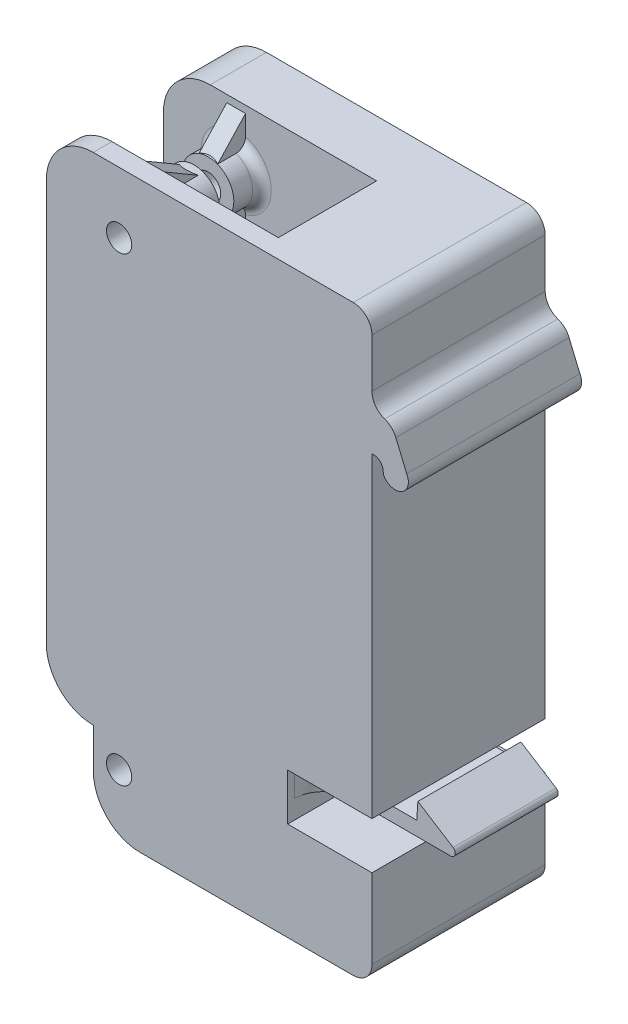
SolidWorks part; units mm, degrees
ref_plane "Alzado" through (0, 0, 0) normal (0, 0, 1) x (1, 0, 0)
ref_plane "Planta" through (0, 0, 0) normal (0, 1, 0) x (1, 0, 0)
ref_plane "Vista lateral" through (0, 0, 0) normal (1, 0, 0) x (0, 0, -1)
sketch "Croquis1" plane through (0, 0, 0) normal (0, 0, 1) x (1, 0, 0)
  line L0 (0, 23.25) -> (0, -23.25)
  circle A0 centre (0, 24.6) radius 1.35
  circle A1 centre (0, -24.6) radius 1.35
  circle A2 centre (0, 24.6) radius 2.75
  circle A3 centre (0, -24.6) radius 2.75
  point P7 (0, 23.25)
  point P8 (0, -23.25)
  dimension "D2" = 2.7
  dimension "D3" = 5.5
  dimension "D4" = 5.5
  dimension "D1" = 46.5
extrude "Saliente-Extruir1" add sketch "Croquis1" against normal blind 6 contours A2 A0 | A3 A1 region at (-1.8895, 26.4895, 0) region at (1.8895, -22.7105, 0)
ref_plane "Plano1" through (0, 0, 1.5) normal (0, 0, 1) x (1, 0, 0)
sketch "Croquis2" plane through (0, 0, 1.5) normal (0, 0, 1) x (1, 0, 0)
  circle A0 centre (0, -24.6) radius 2.75 construction
  circle A1 centre (0, 24.6) radius 2.75 construction
  circle A2 centre (0, -24.6) radius 2.75
  circle A3 centre (0, 24.6) radius 2.75
  circle A4 centre (0, 24.6) radius 1.35 construction
  circle A5 centre (0, -24.6) radius 1.35 construction
  circle A6 centre (0, 24.6) radius 1.35
  circle A7 centre (0, -24.6) radius 1.35
extrude "Saliente-Extruir2" add sketch "Croquis2" along normal blind 8 separate body
ref_plane "Plano2" through (0, 0, 9.5) normal (0, 0, 1) x (1, 0, 0)
sketch "Croquis4" plane through (0, 0, 9.5) normal (0, 0, 1) x (1, 0, 0)
  line L0 (0, 24.6) -> (0, -24.6) construction
  line L1 (15, -31.1189) -> (-7.768, -31.1189)
  line L2 (15, -31.1189) -> (15, 31.1189)
  line L3 (15, 31.1189) -> (-7.768, 31.1189)
  line L4 (-7.768, -31.1189) -> (-7.768, 31.1189)
  line L5 (15, -31.1189) -> (-7.768, 31.1189) construction
  line L6 (15, 31.1189) -> (-7.768, -31.1189) construction
  circle A0 centre (0, -24.6) radius 2.75 construction
  circle A1 centre (0, 24.6) radius 2.75 construction
  circle A2 centre (0, -24.6) radius 2.75
  circle A3 centre (0, 24.6) radius 2.75
  point P0 (3.616, 0)
  dimension "D1" = 15
extrude "Saliente-Extruir3" add sketch "Croquis4" against normal blind 2
sketch "Croquis5" plane through (0, 0, 7.5) normal (0, 0, -1) x (-1, 0, 0)
  line L1 (2.75, -21.85) -> (7.768, -21.85)
  line L2 (2.75, -21.85) -> (2.75, -31.1189)
  line L3 (2.75, -31.1189) -> (7.768, -31.1189)
  line L4 (7.768, -21.85) -> (7.768, -31.1189)
  circle A0 centre (0, -24.6) radius 2.75 construction
  circle A1 centre (0, -24.6) radius 2.75 construction
  point P5 (0, -21.85)
extrude "Cortar-Extruir1" cut sketch "Croquis5" against normal blind 2
fillet "Redondeo1" radius 5 3 edges at (-7.768, 31.1189, 8.5) (-2.75, -31.1189, 8.5) (-7.768, -21.85, 8.5)
ref_plane "Plano3" through (0, 0, -6) normal (0, 0, -1) x (-1, 0, 0)
sketch "Croquis6" plane through (0, 0, -6) normal (0, 0, -1) x (-1, 0, 0)
  line L0 (0, 0) -> (7.768, 0) construction
  line L1 (2.768, -31.1189) -> (-15, -31.1189)
  line L2 (-15, 31.1189) -> (-15, -31.1189)
  line L8 (7.768, -26.1189) -> (7.768, 26.1189)
  line L9 (2.768, 31.1189) -> (-15, 31.1189)
  arc A0 (7.768, -26.1189) -> (2.768, -31.1189) centre (2.768, -26.1189) cw
  circle A1 centre (0, -24.6) radius 2.75 construction
  circle A2 centre (0, 24.6) radius 2.75 construction
  circle A3 centre (0, -24.6) radius 2.75
  arc A11 (7.768, 26.1189) -> (2.768, 31.1189) centre (2.768, 26.1189) ccw
  circle A12 centre (0, 24.6) radius 2.75
extrude "Saliente-Extruir4" add sketch "Croquis6" against normal blind 3
sketch "Croquis7" plane through (0, 0, -6) normal (0, 0, -1) x (-1, 0, 0)
  line L4 (7.768, -26.1189) -> (7.768, 26.1189)
  line L5 (2.768, 31.1189) -> (-15, 31.1189)
  line L6 (-15, 31.1189) -> (-15, -31.1189)
  line L7 (-15, -31.1189) -> (2.768, -31.1189)
  line L8 (7.768, -26.1189) -> (7.768, 26.1189)
  line L9 (2.768, 31.1189) -> (-15, 31.1189)
  line L10 (-15, 31.1189) -> (-15, -31.1189)
  line L11 (-15, -31.1189) -> (2.768, -31.1189)
  circle A0 centre (0, -24.6) radius 1.35 construction
  circle A1 centre (0, 24.6) radius 1.35 construction
  arc A2 (2.768, -31.1189) -> (7.768, -26.1189) centre (2.768, -26.1189) ccw
  arc A3 (7.768, 26.1189) -> (2.768, 31.1189) centre (2.768, 26.1189) ccw
  arc A4 (2.768, -31.1189) -> (7.768, -26.1189) centre (2.768, -26.1189) ccw
  arc A5 (7.768, 26.1189) -> (2.768, 31.1189) centre (2.768, 26.1189) ccw
  circle A6 centre (0, -24.6) radius 1.35
  circle A7 centre (0, 24.6) radius 1.35
  dimension "D1" = 0
extrude "Saliente-Extruir6" add sketch "Croquis7" along normal blind 3
ref_plane "Plano4" through (15, 0, 0) normal (1, 0, 0) x (0, 0, -1)
sketch "Croquis9" plane through (15, 0, 0) normal (1, 0, 0) x (0, 0, -1)
  line L1 (-9.5, 31.1189) -> (9, 31.1189)
  line L2 (-9.5, 31.1189) -> (-9.5, -31.1189)
  line L3 (-9.5, -31.1189) -> (9, -31.1189)
  line L4 (9, 31.1189) -> (9, -31.1189)
extrude "Saliente-Extruir7" add sketch "Croquis9" along normal blind 12
ref_plane "Plano5" through (0, 0, 0.25) normal (0, 0, 1) x (1, 0, 0)
sketch "Croquis10" plane through (0, 0, -9) normal (0, 0, -1) x (-1, 0, 0)
  line L0 (-27, 21.2078) -> (-27.7857, 21.2078)
  line L1 (-27, -31.1189) -> (-27, 31.1189) construction
  line L2 (-27.7857, 21.2078) -> (-28.018, 18.5571)
  line L3 (-29.036, 18.5897) -> (-29.036, 23.6091)
  line L4 (-28.2044, 25.2323) -> (-27, 26.0992)
  line L5 (-27, 26.0992) -> (-27, 21.2078)
  arc A0 (-28.018, 18.5571) -> (-29.036, 18.5897) centre (-28.5261, 18.6017) cw
  arc A1 (-29.036, 23.6091) -> (-28.2044, 25.2323) centre (-27.036, 23.6091) cw
  dimension "D1" = 2
sketch "Croquis11" plane through (0, 0, 0.25) normal (0, 0, 1) x (1, 0, 0)
  line L5 (27, 22.4051) -> (27, 18.1284)
  line L6 (30.7136, 18.1284) -> (29.1816, 21.7903)
  line L7 (28.0402, 18.1284) -> (28.2529, 16.762)
  line L8 (27, 18.1284) -> (28.0402, 18.1284)
  line L9 (29.1816, 21.7903) -> (27, 22.4051)
  line L10 (27, 31.1189) -> (27, -31.1189) construction
  arc A3 (28.2529, 16.762) -> (30.7136, 18.1284) centre (29.4832, 17.4452) ccw
extrude "Saliente-Extruir8" add sketch "Croquis11" along normal mid plane 18.5
sketch "Croquis12" plane through (0, 0, 0.25) normal (0, 0, 1) x (1, 0, 0)
  line L0 (21, -17.1189) -> (28.0356, -17.1189)
  line L1 (2.25, -31.1189) -> (27, -31.1189) construction
  line L2 (28.0356, -17.1189) -> (28.1533, -15.3189)
  line L3 (28.1533, -15.3189) -> (28.2001, -15.3485)
  line L4 (27.7384, -17.1189) -> (28.8359, -17.1189) construction
  line L5 (27, -17.1189) -> (27, -18.6189)
  line L6 (27, 18.1284) -> (27, -31.1189) construction
  line L7 (27, -18.6189) -> (33.3679, -18.6189)
  line L8 (33.3679, -18.6189) -> (28.2001, -15.3485)
  line L9 (27, -18.6189) -> (21, -18.6189)
  line L10 (21, -18.6189) -> (21, -17.1189)
  dimension "D1" = 14
  dimension "D2" = 1.8
  dimension "D3" = 1.5
  dimension "D4" = 6
extrude "Saliente-Extruir10" add sketch "Croquis12" along normal mid plane 11 contours L7 L8 L3 L2 L0 L10 L9
fillet "Redondeo5" radius 0.5 1 edges at (33.3679, -18.6189, 0.25)
fillet "Redondeo7" radius 2 2 edges at (27, -31.1189, 0.25) (27, 31.1189, 0.25)
fillet "Redondeo9" radius 2 1 edges at (27, 22.4051, 0.25)
fillet "Redondeo10" radius 1 1 edges at (28.0402, 18.1284, 0.25)
sketch "Croquis13" plane through (0, 0, 9.5) normal (0, 0, 1) x (1, 0, 0)
  line L0 (27, -17.1189) -> (18, -17.1189)
  line L1 (18, -17.1189) -> (18, -18.6189)
  line L2 (18, -18.6189) -> (27, -18.6189)
  line L3 (27, 18.1284) -> (27, -29.1189) construction
  line L6 (18, -18.6189) -> (27, -18.6189)
  line L7 (18, -18.6189) -> (18, -20.6189)
  line L8 (18, -20.6189) -> (27, -20.6189)
  line L9 (27, -18.6189) -> (27, -20.6189)
  line L10 (18, -17.1189) -> (27, -17.1189)
  line L11 (18, -17.1189) -> (18, -15.6189)
  line L12 (18, -15.6189) -> (27, -15.6189)
  line L13 (27, -17.1189) -> (27, -15.6189)
  line M9 (27, -29.1189) -> (27, 18.1284)
  dimension "D1" = 9
  dimension "D2" = 2
  dimension "D3" = 1.5
extrude "Cortar-Extruir2" cut sketch "Croquis13" against normal through all contours L12 L11 L0 M9 | L7 L8 L2 M9 region at (22.5, -16.3689, 9.5) region at (22.5, -19.6189, 9.5)
ref_plane "Plano6" through (27, 0, 0) normal (1, 0, 0) x (0, 0, -1)
sketch "Croquis14" plane through (27, 0, 0) normal (1, 0, 0) x (0, 0, -1)
  line L0 (9, -18.6189) -> (9, -17.1189) construction
  line L1 (9, -17.1189) -> (5.25, -17.1189) construction
  line L2 (5.25, -17.1189) -> (5.25, -18.6189) construction
  line L3 (5.25, -18.6189) -> (9, -18.6189) construction
  line L4 (-5.75, -18.6189) -> (-5.75, -17.1189) construction
  line L5 (-5.75, -17.1189) -> (-9.5, -17.1189) construction
  line L6 (-9.5, -17.1189) -> (-9.5, -18.6189) construction
  line L7 (-9.5, -18.6189) -> (-5.75, -18.6189) construction
  line L8 (9, -18.6189) -> (9, -17.1189)
  line L9 (9, -17.1189) -> (5.25, -17.1189)
  line L10 (5.25, -17.1189) -> (5.25, -18.6189)
  line L11 (5.25, -18.6189) -> (9, -18.6189)
  line L12 (-5.75, -18.6189) -> (-5.75, -17.1189)
  line L13 (-5.75, -17.1189) -> (-9.5, -17.1189)
  line L14 (-9.5, -17.1189) -> (-9.5, -18.6189)
  line L15 (-9.5, -18.6189) -> (-5.75, -18.6189)
extrude "Cortar-Extruir3" cut sketch "Croquis14" against normal up to surface (9 mm away) up to face at (18, -19.6189, 0.25)
fillet "Redondeo12" radius 3 2 edges at (18, -17.8689, 5.75) (18, -17.8689, -5.25)
fillet "Redondeo13" radius 3 1 edges at (18, -17.1189, 0.25)
sketch "Croquis15" plane through (0, 0, 0) normal (0, 0, 1) x (1, 0, 0)
  line L0 (0, 27.35) -> (0, 21.85) construction
  circle A0 centre (0, 24.6) radius 2.75 construction
ref_plane "Plano7" through (0, 0, 0) normal (-1, 0, 0) x (0, -1, 0)
sketch "Croquis16" plane through (0, 0, 0) normal (-1, 0, 0) x (0, -1, 0)
  line L0 (-27.1247, 0) -> (-30.35, -3)
  line L2 (-27.35, 0) -> (-27.35, -3) construction
  line L3 (-26.1189, -3) -> (-31.1189, -3) construction
  line L4 (-27.35, 0) -> (-21.85, 0) construction
  dimension "D1" = 3
rib "Nervio13" sketch "Croquis16" sketch "Croquis16" thickness 2 extrusion direction parallel to sketch draft on no parameters "D1"=2
sketch "Croquis17" plane through (0, 0, 0) normal (-1, 0, 0) x (0, -1, 0)
  line L0 (-22.0095, -0.2021) -> (-18.85, -3)
  line L1 (-31.1189, -3) -> (31.1189, -3) construction
  line L2 (-21.85, -3) -> (-21.85, 0) construction
  dimension "D1" = 3
rib "Nervio14" sketch "Croquis17" sketch "Croquis17" thickness 2 extrusion direction parallel to sketch draft on no parameters "D1"=2
sketch "Croquis19" plane through (0, 0, 0) normal (-1, 0, 0) x (0, -1, 0)
  line L0 (22.0326, -0.2622) -> (18.85, -3)
  line L1 (-31.1189, -3) -> (31.1189, -3) construction
  line L2 (21.85, 0) -> (21.85, -3) construction
  dimension "D1" = 3
rib "Nervio16" sketch "Croquis19" sketch "Croquis19" thickness 2 extrusion direction parallel to sketch draft on no parameters "D1"=2
sketch "Croquis20" plane through (0, 0, 0) normal (-1, 0, 0) x (0, -1, 0)
  line L0 (27.0832, -0.3078) -> (30.35, -3)
  line L1 (-31.1189, -3) -> (31.1189, -3) construction
  line L2 (27.35, -3) -> (27.35, 0) construction
  dimension "D1" = 3
rib "Nervio17" sketch "Croquis20" sketch "Croquis20" thickness 2 extrusion direction parallel to sketch draft on no parameters "D1"=2
sketch "Croquis21" plane through (0, 0, 0) normal (-1, 0, 0) x (0, -1, 0)
  line L0 (-30.35, 7.5) -> (-27.0505, 1.8669)
  line L1 (31.1189, 7.5) -> (-31.1189, 7.5) construction
  line L2 (-27.35, 7.5) -> (-27.35, 1.5) construction
  dimension "D1" = 3
rib "Nervio18" sketch "Croquis21" sketch "Croquis21" thickness 2 extrusion direction parallel to sketch draft on no parameters "D1"=2
sketch "Croquis22" plane through (0, 0, 0) normal (-1, 0, 0) x (0, -1, 0)
  line L0 (-22.1331, 1.8884) -> (-18.85, 7.5)
  line L1 (31.1189, 7.5) -> (-31.1189, 7.5) construction
  line L2 (-21.85, 1.5) -> (-21.85, 7.5) construction
  dimension "D1" = 3
rib "Nervio19" sketch "Croquis22" sketch "Croquis22" thickness 2 extrusion direction parallel to sketch draft on no parameters "D1"=2
sketch "Croquis23" plane through (0, 0, 0) normal (-1, 0, 0) x (0, -1, 0)
  line L0 (22.129, 1.7917) -> (18.85, 7.5)
  line L1 (31.1189, 7.5) -> (-31.1189, 7.5) construction
  line L2 (21.85, 7.5) -> (21.85, 1.5) construction
  dimension "D1" = 3
rib "Nervio20" sketch "Croquis23" sketch "Croquis23" thickness 2 extrusion direction parallel to sketch draft on no parameters "D1"=2
sketch "Croquis24" plane through (0, 0, 0) normal (-1, 0, 0) x (0, -1, 0)
  line L0 (26.0694, 1.7611) -> (29.35, 7.5)
  line L1 (26.1189, 7.5) -> (31.1189, 7.5) construction
  line L2 (27.35, 1.5) -> (27.35, 7.5) construction
  dimension "D1" = 2
rib "Nervio22" sketch "Croquis24" sketch "Croquis24" thickness 2 extrusion direction parallel to sketch draft on no parameters "D1"=2
fillet "Redondeo14" radius 1 7 edges at (2.75, 24.6, 7.5) (-2.75, 24.6, 7.5) (2.75, 24.6, -3) (-2.75, 24.6, -3) (2.75, -24.6, 7.5) (-2.75, -24.6, -3) (2.75, -24.6, -3)
fillet "Redondeo15" radius 2 1 edges at (29.1816, 21.7903, 0.25)
